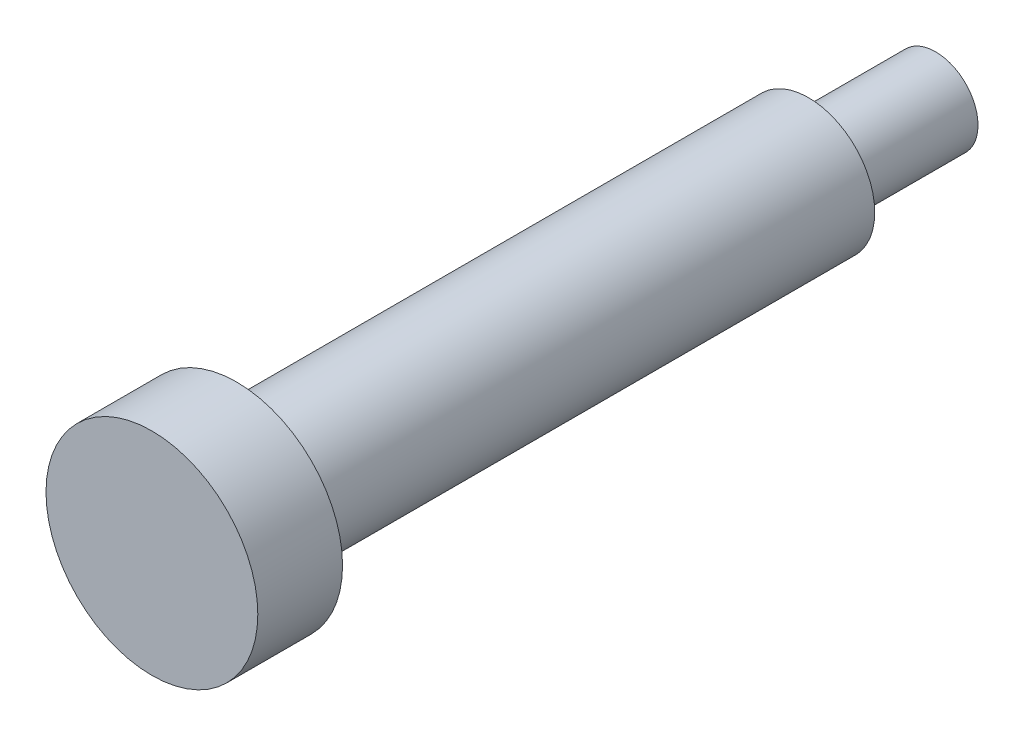
SolidWorks part; units mm, degrees
material "Stainless Steel (ferritic)"
ref_plane "Front Plane" through (0, 0, 0) normal (0, 0, 1) x (1, 0, 0)
ref_plane "Top Plane" through (0, 0, 0) normal (0, 1, 0) x (1, 0, 0)
ref_plane "Right Plane" through (0, 0, 0) normal (1, 0, 0) x (0, 0, -1)
sketch "Sketch1" plane through (0, 0, 0) normal (0, 0, 1) x (1, 0, 0)
  circle A0 centre (0, 0) radius 5
  circle A1 centre (0, 0) radius 3.125
  circle A2 centre (0, 0) radius 2
  dimension "D1" = 4
  dimension "D2" = 6.25
  dimension "D3" = 10
extrude "Boss-Extrude1" add sketch "Sketch1" along normal blind 4 contours A2 | A1 A2 | A0 A1 region at (-4.8586, 0, 0) region at (-3.0366, 0, 0) region at (0, 0, 0)
extrude "Boss-Extrude2" add sketch "Sketch1<3>" against normal blind 27 contours A2 | A1 A2 region at (-3.0366, 0, 0) region at (0, 0, 0)
sketch "Sketch1<3>" plane through (0, 0, 0) normal (0, 0, 1) x (1, 0, 0) same geometry as "Sketch1"
extrude "Boss-Extrude3" add sketch "Sketch1<4>" against normal blind 6 from surface contours A2 region at (0, 0, 0) starting at face at (3.125, 0, -27)
sketch "Sketch1<4>" plane through (0, 0, 0) normal (0, 0, 1) x (1, 0, 0) same geometry as "Sketch1"
